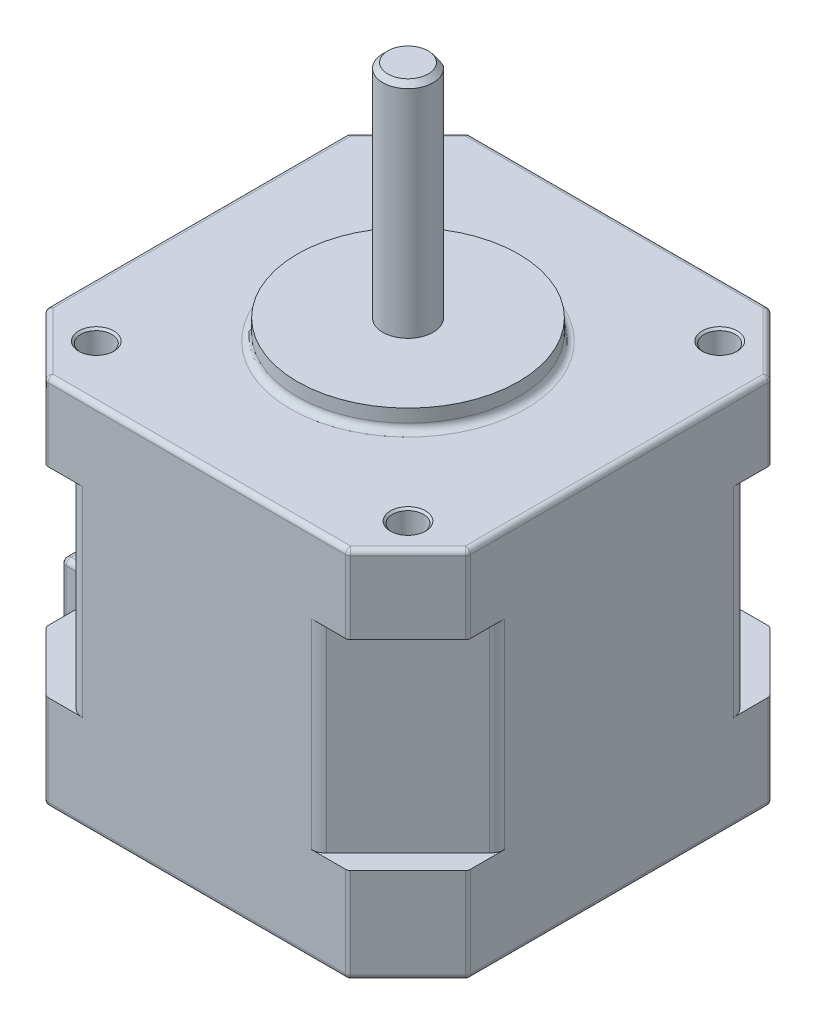
SolidWorks part; units mm, degrees
ref_plane "Front Plane" through (0, 0, 0) normal (0, 0, 1) x (1, 0, 0)
ref_plane "Top Plane" through (0, 0, 0) normal (0, 1, 0) x (1, 0, 0)
ref_plane "Right Plane" through (0, 0, 0) normal (1, 0, 0) x (0, 0, -1)
sketch "Sketch1" plane through (0, 0, 0) normal (0, 1, 0) x (1, 0, 0)
  line L0 (-42, 36) -> (-36, 42)
  line L1 (-6, 0) -> (-36, 0)
  line L2 (0, 6) -> (0, 36)
  line L3 (-6, 42) -> (-36, 42)
  line L4 (-42, 6) -> (-42, 12.75)
  line L5 (0, 36) -> (-6, 42)
  line L6 (-6, 0) -> (0, 6)
  line L7 (-36, 0) -> (-42, 6)
  line L8 (-21, 42) -> (-21, 0) construction
  line L9 (-42, 21) -> (0, 21) construction
  line L10 (-42, 29.25) -> (-47.25, 29.25)
  line L11 (-47.25, 29.25) -> (-47.25, 12.75)
  line L12 (-47.25, 12.75) -> (-42, 12.75)
  line L13 (-42, 29.25) -> (-42, 36)
  circle A0 centre (-21, 21) radius 4.5
  point P0 (0, 0)
  point P1 (-42, 42)
  point P2 (0, 42)
  point P3 (-42, 0)
  dimension "D11" = 9
  dimension "D1" = 42
  dimension "D2" = 42
  dimension "D3" = 6
  dimension "D4" = 45
  dimension "D5" = 6
  dimension "D6" = 45
  dimension "D7" = 6
  dimension "D8" = 45
  dimension "D9" = 6
  dimension "D10" = 45
  dimension "D12" = 5.25
  dimension "D13" = 16.5
extrude "Boss-Extrude1" add sketch "Sketch1" along normal blind 9.5
sketch "Sketch2" plane through (0, 9.5, 0) normal (0, 1, 0) x (1, 0, 0)
  line L1 (-33, 42) -> (-9, 42)
  line L2 (0, 33) -> (0, 9)
  line L3 (-9, 0) -> (-33, 0)
  line L5 (-42, 33) -> (-42, 9)
  line L6 (-33, 42) -> (-42, 33)
  line L7 (-9, 42) -> (0, 33)
  line L8 (0, 9) -> (-9, 0)
  line L9 (-33, 0) -> (-42, 9)
  line L10 (-6, 42) -> (-36, 42) construction
  point P1 (-42, 42)
  point P5 (0, 42)
  point P6 (0, 0)
  point P8 (-42, 0)
  dimension "D1" = 9
  dimension "D2" = 45
  dimension "D3" = 9
  dimension "D4" = 45
  dimension "D5" = 9
  dimension "D6" = 45
  dimension "D7" = 9
  dimension "D8" = 45
extrude "Boss-Extrude2" add sketch "Sketch2" along normal blind 19.88
sketch "Sketch3" plane through (0, 29.38, 0) normal (0, 1, 0) x (1, 0, 0)
  line L0 (-42, 6) -> (-42, 36)
  line L1 (-42, 36) -> (-36, 42)
  line L2 (-36, 42) -> (-6, 42)
  line L3 (-6, 42) -> (0, 36)
  line L4 (0, 36) -> (0, 6)
  line L5 (0, 6) -> (-6, 0)
  line L6 (-6, 0) -> (-36, 0)
  line L7 (-36, 0) -> (-42, 6)
  line L8 (-36, 6) -> (-6, 6) construction
  line L9 (-6, 6) -> (-6, 36) construction
  line L10 (-6, 36) -> (-36, 36) construction
  line L11 (-21, 6) -> (-21, 0) construction
  line L12 (-6, 21) -> (0, 21) construction
  circle A0 centre (-36, 6) radius 1.55
  circle A1 centre (-6, 36) radius 1.55
  circle A2 centre (-36, 36) radius 1.55
  circle A3 centre (-6, 6) radius 1.55
  point P27 (-6, 36.286)
  point P29 (-36.2359, 36)
  point P31 (-6, 5.6925)
  dimension "D3" = 3.1
  dimension "D1" = 30
  dimension "D2" = 30
extrude "Boss-Extrude3" add sketch "Sketch3" along normal blind 7.72 contours L1 L2 L3 L4 L5 L6 L7 L0
sketch "Sketch5" plane through (0, 37.1, 0) normal (0, 1, 0) x (1, 0, 0)
  line L0 (-36.5, 5.5) -> (-5.5, 5.5) construction
  line L1 (-5.5, 5.5) -> (-5.5, 36.5) construction
  line L2 (-5.5, 36.5) -> (-36.5, 36.5) construction
  line L3 (-21, 5.5) -> (-21, -1.0949) construction
  line L4 (-5.5, 21) -> (0, 21) construction
  line L6 (-42, 6) -> (-42, 36) construction
  circle A0 centre (-36.5, 5.5) radius 1.55
  circle A1 centre (-5.5, 36.5) radius 1.55
  circle A2 centre (-36.5, 36.5) radius 1.55
  circle A3 centre (-5.5, 5.5) radius 1.55
  dimension "D3" = 3.1
  dimension "D1" = 31
  dimension "D2" = 31
  dimension "D4" = 21
  dimension "D5" = 21
extrude "Cut-Extrude1" cut sketch "Sketch5" against normal blind 7.5
sketch "Sketch6" plane through (0, 37.1, 0) normal (0, 1, 0) x (1, 0, 0)
  line L0 (-42, 21) -> (0, 21) construction
  line L1 (-42, 6) -> (-42, 36) construction
  line L2 (0, 36) -> (0, 6) construction
  circle A0 centre (-21, 21) radius 11
  point P8 (-21, 21)
  dimension "D1" = 22
extrude "Boss-Extrude4" add sketch "Sketch6" along normal blind 2
sketch "Sketch7" plane through (0, 39.1, 0) normal (0, 1, 0) x (1, 0, 0)
  line L0 (-32, 21) -> (-10, 21) construction
  line L1 (-22.5, 23) -> (-19.5, 23)
  circle A0 centre (-21, 21) radius 11 construction
  circle A1 centre (-21, 21) radius 11 construction
  arc A2 (-22.5, 23) -> (-19.5, 23) centre (-21, 21) ccw
  dimension "D1" = 5
  dimension "D2" = 3
extrude "Boss-Extrude5" add sketch "Sketch7" along normal blind 22
chamfer "Chamfer1" distance 0.2 angle 45 4 edges at (-5.5, 37.1, -3.95) (-5.5, 37.1, -34.95) (-36.5, 37.1, -34.95) (-36.5, 37.1, -3.95)
fillet "Fillet1" radius 0.5 45 edges at (-42, 4.75, -12.75) (-42, 4.75, -29.25) (-44.625, 9.5, -12.75) (-44.625, 9.5, -29.25) (-42, 9.5, -21) (-47.25, 4.75, -29.25) (-47.25, 9.5, -21) (-47.25, 4.75, -12.75) (-21, 0, -16.5) (-44.625, 0, -29.25) (-47.25, 0, -21) (-44.625, 0, -12.75) (-42, 0, -9.375) (-39, 0, -3) (-21, 0, 0) (-3, 0, -3) (0, 0, -21) (-3, 0, -39) (-21, 0, -42) (-39, 0, -39) (-42, 0, -32.625) (-6, 4.75, -42) (0, 4.75, -36) (-42, 4.75, -36) (-36, 4.75, -42) (0, 4.75, -6) (-6, 4.75, 0) (-36, 4.75, 0) (-42, 4.75, -6) (-42, 33.24, -36) (-39, 37.1, -39) (-36, 33.24, -42) (-21, 37.1, -42) (-6, 33.24, -42) (0, 33.24, -36) (0, 37.1, -21) (-3, 37.1, -39) (0, 33.24, -6) (-6, 33.24, 0) (-42, 33.24, -6) (-36, 33.24, 0) (-3, 37.1, -3) (-21, 37.1, 0) (-39, 37.1, -3) (-42, 37.1, -21)
fillet "Fillet2" radius 0.7 1 edges at (-21, 37.1, -10)
chamfer "Chamfer2" distance 0.5 angle 45 1 edges at (-21, 61.1, -18.5)
fillet "Fillet3" radius 1.5 8 edges at (-42, 19.44, -33) (-33, 19.44, -42) (-9, 19.44, -42) (0, 19.44, -33) (0, 19.44, -9) (-9, 19.44, 0) (-33, 19.44, 0) (-42, 19.44, -9)
